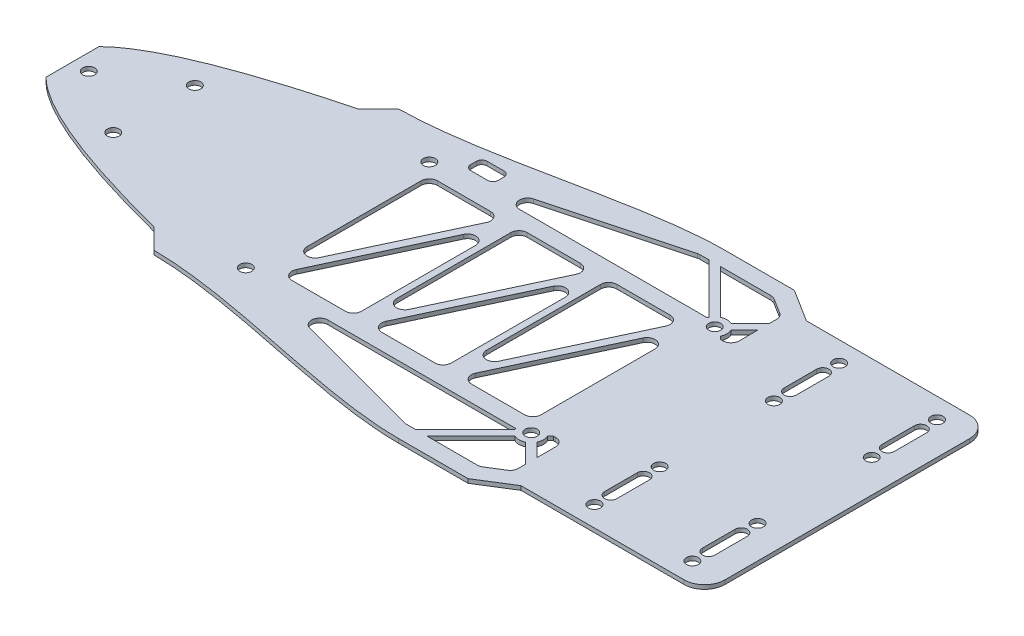
SolidWorks part; units mm, degrees
material "1060 Сплав"
ref_plane "Спереди" through (0, 0, 0) normal (0, 0, 1) x (1, 0, 0)
ref_plane "Сверху" through (0, 0, 0) normal (0, 1, 0) x (1, 0, 0)
ref_plane "Справа" through (0, 0, 0) normal (1, 0, 0) x (0, 0, -1)
sketch "Эскиз1" plane through (0, 0, 0) normal (0, 1, 0) x (1, 0, 0)
  line L0 (-109.2342, 0) -> (114.1892, 0) construction
  line L1 (95, -40) -> (-95, -40)
  line L2 (95, -40) -> (95, 40)
  line L3 (95, 40) -> (-95, 40)
  line L4 (-95, -40) -> (-95, 40)
  line L5 (95, -40) -> (-95, 40) construction
  line L6 (95, 40) -> (-95, -40) construction
  line L7 (50, 35) -> (42, 40)
  line L8 (95, 40) -> (50, 40)
  line L9 (95, 40) -> (95, 35)
  line L10 (95, 35) -> (50, 35)
  line L11 (50, 40) -> (50, 35)
  line L12 (95, -40) -> (50, -40)
  line L13 (95, -40) -> (95, -35)
  line L14 (95, -35) -> (50, -35)
  line L15 (50, -40) -> (50, -35)
  line L16 (50, -35) -> (42, -40)
  point P0 (0, 0)
  dimension "D1" = 190
  dimension "D2" = 80
  dimension "D3" = 45
  dimension "D4" = 70
  dimension "D5" = 8
extrude "Габариты" add sketch "Эскиз1" along normal blind 1 contours L16 L14 L2 L10 L7 L3 L4 L1 region at (-2.3466, 0, 0)
sketch "Эскиз2" plane through (0, 0, 0) normal (0, 1, 0) x (1, 0, 0)
  line L0 (-115.1505, 0) -> (106.9824, 0) construction
  line L1 (-95, -40) -> (-95, 40) construction
  line L2 (-95, 6.4911) -> (-95, -6.4911)
  line L3 (-95, 6.4911) -> (-95, -6.4911)
  line L5 (42, 40) -> (-95, 40) construction
  line L6 (42, -40) -> (-95, -40) construction
  line L7 (25, 40) -> (-95, 40)
  line L9 (-95, 40) -> (-95, 6.4911)
  line L10 (-95, -6.4911) -> (-95, -40)
  line L11 (-95, -40) -> (25, -40)
  line L12 (-50, 25.0267) -> (-45, 30)
  line L13 (-50, -25.0267) -> (-45, -30)
  parabola Q0 (25, -40) -> (25, 40) focus (-95, 0) apex (-98.2456, 0)
  spline S0 degree 3 poles (-45, 30) (-23.3831, 30.2616) (4.7804, 40) (25, 40) knots 0 0 0 0 1 1 1 1
  spline S1 degree 3 poles (-45, -30) (-23.3831, -30.2616) (4.7804, -40) (25, -40) knots 0 0 0 0 1 1 1 1
  point P15 (-95, 0)
  dimension "D1" = 120
  dimension "D2" = 45
  dimension "D3" = 50
  dimension "D4" = 60
extrude "Форма основы" cut sketch "Эскиз2" along normal through all contours L9 Q0 L7 | L11 Q0 L10 region at (-61.4598, 0, 30.4598) region at (-61.4598, 0, -30.4598)
sketch "Эскиз3" plane through (0, 0, 0) normal (0, 1, 0) x (1, 0, 0)
  line L0 (-107.3808, 0) -> (106.9824, 0) construction
  line L1 (75, 38.7487) -> (75, -39.5456) construction
  line L2 (95, 35) -> (50, 35) construction
  line L3 (63, 26) -> (63, 18) construction
  line L4 (95, -35) -> (95, 35) construction
  line L5 (64.5, 26) -> (64.5, 18)
  line L6 (61.5, 26) -> (61.5, 18)
  line L7 (87, 26) -> (87, 18) construction
  line L8 (85.5, 26) -> (85.5, 18)
  line L9 (88.5, 26) -> (88.5, 18)
  line L10 (63, -26) -> (63, -18) construction
  line L11 (64.5, -26) -> (64.5, -18)
  line L12 (61.5, -26) -> (61.5, -18)
  line L13 (87, -26) -> (87, -18) construction
  line L14 (85.5, -26) -> (85.5, -18)
  line L15 (88.5, -26) -> (88.5, -18)
  line L16 (95, -35) -> (50, -35) construction
  line L20 (95, -35) -> (95, -30)
  line L21 (95, 35) -> (90, 35)
  line L22 (95, -35) -> (90, -35)
  line L24 (95, 30) -> (95, 35)
  circle A0 centre (63, 30) radius 1.475
  circle A1 centre (63, 14) radius 1.475
  circle A2 centre (87, 14) radius 1.475
  circle A3 centre (87, 30) radius 1.475
  circle A4 centre (87, -14) radius 1.475
  circle A5 centre (87, -30) radius 1.475
  circle A6 centre (63, -14) radius 1.475
  circle A7 centre (63, -30) radius 1.475
  arc A8 (64.5, 26) -> (61.5, 26) centre (63, 26) ccw
  arc A9 (61.5, 18) -> (64.5, 18) centre (63, 18) ccw
  arc A10 (85.5, 26) -> (88.5, 26) centre (87, 26) cw
  arc A11 (88.5, 18) -> (85.5, 18) centre (87, 18) cw
  arc A12 (64.5, -26) -> (61.5, -26) centre (63, -26) cw
  arc A13 (61.5, -18) -> (64.5, -18) centre (63, -18) cw
  arc A14 (85.5, -26) -> (88.5, -26) centre (87, -26) ccw
  arc A15 (88.5, -18) -> (85.5, -18) centre (87, -18) ccw
  arc A16 (90, -35) -> (95, -30) centre (90, -30) ccw
  arc A17 (95, 30) -> (90, 35) centre (90, 30) ccw
  point P11 (63, 22)
  point P34 (87, 22)
  point P41 (63, -22)
  point P48 (87, -22)
  dimension "D2" = 2.95
  dimension "D9" = 5
  dimension "D4" = 16
  dimension "D5" = 5
  dimension "D3" = 24
  dimension "D1" = 20
  dimension "D6" = 4
  dimension "D7" = 4
  dimension "D8" = 3
extrude "Крепёж колёс" cut sketch "Эскиз3" along direction (0, 1, 0) on the side of the normal through all
sketch "Эскиз5" plane through (0, 0, 0) normal (0, 1, 0) x (1, 0, 0)
  line L0 (-94.6705, 0) -> (98.4358, 0) construction
  line L1 (-95, -6.4911) -> (-95, 6.4911) construction
  line L2 (-75, 10) -> (-75, -10) construction
  circle A0 centre (-75, 10) radius 1.475
  circle A1 centre (-75, -10) radius 1.475
  circle A2 centre (-91, 0) radius 1.475
  dimension "D1" = 2.95
  dimension "D4" = 16
  dimension "D2" = 20
  dimension "D3" = 20
extrude "Крепёж датчиков" cut sketch "Эскиз5" along normal blind 3
sketch "Эскиз6" plane through (0, 0, 0) normal (0, 1, 0) x (1, 0, 0)
  line L0 (-93.9533, 0) -> (93.2361, 0) construction
  circle A0 centre (-30, 22.5) radius 1.475
  circle A1 centre (40, 22.5) radius 1.475
  circle A2 centre (40, -22.5) radius 1.475
  circle A3 centre (-30, -22.5) radius 1.475
  dimension "D1" = 2.95
  dimension "D2" = 70
  dimension "D3" = 45
  dimension "D4" = 20
extrude "Крепёж платы" cut sketch "Эскиз6" along normal up to next
sketch "Эскиз7" plane through (0, 0, 0) normal (0, 1, 0) x (1, 0, 0)
  line L0 (-93.5382, 0) -> (96.5724, 0) construction
  line L6 (-30, -22.5) -> (40, 22.5) construction
  line L7 (-30, 22.5) -> (40, -22.5) construction
  line L10 (-8.6072, -19.5) -> (-21.6539, -19.5)
  line L12 (-11.9534, 19.5) -> (-25, 19.5)
  line L13 (-27, -10.4786) -> (-27, 17.5)
  line L14 (13.9587, -12.1877) -> (-30, 22.5) construction
  line L16 (-23.1874, -11.3238) -> (-10.1408, 16.6548)
  line L18 (-10.4199, 11.3238) -> (-23.4665, -16.6548)
  line L20 (-6.6072, -17.5) -> (-6.6072, 10.4786)
  line L33 (-5, -10.4786) -> (-5, 17.5)
  line L34 (-5, 23.9923) -> (-5, -26.1687) construction
  line L35 (-27, -10.4786) -> (-27, -19.5) construction
  line L36 (-6.6072, 10.4786) -> (-6.6072, 19.5) construction
  line L37 (-21.6539, -19.5) -> (-27, -19.5) construction
  line L38 (-11.9534, 19.5) -> (-6.6072, 19.5) construction
  line L39 (-25, -12.4786) -> (-19.3057, -12.4786)
  line L40 (-8.6072, 12.4786) -> (-10.7097, 12.4786)
  line L41 (10.0466, 19.5) -> (-3, 19.5)
  line L42 (-1.1874, -11.3238) -> (11.8592, 16.6548)
  line L43 (11.5801, 11.3238) -> (-1.4665, -16.6548)
  line L44 (15.3928, -17.5) -> (15.3928, 10.4786)
  line L45 (13.3928, -19.5) -> (0.3461, -19.5)
  line L46 (17, -10.4786) -> (17, 17.5)
  line L47 (32.0466, 19.5) -> (19, 19.5)
  line L48 (20.8126, -11.3238) -> (33.8592, 16.6548)
  line L49 (33.5801, 11.3238) -> (20.5335, -16.6548)
  line L50 (37.3928, -17.5) -> (37.3928, 10.4786)
  line L51 (35.3928, -19.5) -> (22.3461, -19.5)
  arc A0 (-11.9534, 19.5) -> (-10.1408, 16.6548) centre (-11.9534, 17.5) cw
  arc A1 (-25, 19.5) -> (-27, 17.5) centre (-25, 17.5) ccw
  arc A2 (-27, -10.4786) -> (-23.1874, -11.3238) centre (-25, -10.4786) ccw
  arc A3 (-23.4665, -16.6548) -> (-21.6539, -19.5) centre (-21.6539, -17.5) ccw
  arc A4 (-8.6072, -19.5) -> (-6.6072, -17.5) centre (-8.6072, -17.5) ccw
  arc A5 (-6.6072, 10.4786) -> (-10.4199, 11.3238) centre (-8.6072, 10.4786) ccw
  arc A6 (-3, 19.5) -> (-5, 17.5) centre (-3, 17.5) ccw
  arc A7 (10.0466, 19.5) -> (11.8592, 16.6548) centre (10.0466, 17.5) cw
  arc A8 (-5, -10.4786) -> (-1.1874, -11.3238) centre (-3, -10.4786) ccw
  arc A9 (15.3928, 10.4786) -> (11.5801, 11.3238) centre (13.3928, 10.4786) ccw
  arc A10 (13.3928, -19.5) -> (15.3928, -17.5) centre (13.3928, -17.5) ccw
  arc A11 (-1.4665, -16.6548) -> (0.3461, -19.5) centre (0.3461, -17.5) ccw
  arc A12 (19, 19.5) -> (17, 17.5) centre (19, 17.5) ccw
  arc A13 (32.0466, 19.5) -> (33.8592, 16.6548) centre (32.0466, 17.5) cw
  arc A14 (17, -10.4786) -> (20.8126, -11.3238) centre (19, -10.4786) ccw
  arc A15 (37.3928, 10.4786) -> (33.5801, 11.3238) centre (35.3928, 10.4786) ccw
  arc A16 (35.3928, -19.5) -> (37.3928, -17.5) centre (35.3928, -17.5) ccw
  arc A17 (20.5335, -16.6548) -> (22.3461, -19.5) centre (22.3461, -17.5) ccw
  point P32 (-6.6072, 19.5)
  dimension "D1" = 3
  dimension "D4" = 2
  dimension "D5" = 2
  dimension "D7" = 3
  dimension "D2" = 3
  dimension "D3" = 25
  dimension "D6" = 2
extrude "Облегчение 1" cut sketch "Эскиз7" along normal through all contours L16 A0 L12 A1 L13 A2 | L18 A3 L10 A4 L20 A5 | L33 A6 L41 A7 L42 A8 | L43 A11 L45 A10 L44 A9 | L46 A12 L47 A13 L48 A14 | L49 A17 L51 A16 L50 A15
sketch "Эскиз8" plane through (0, 0, 0) normal (0, 1, 0) x (1, 0, 0)
  line L0 (-98.4956, 0) -> (99.5433, 0) construction
  line L1 (37.1716, 23.5) -> (-8.8722, 23.5)
  line L2 (-9.3898, 27.4319) -> (24.5577, 36.5281)
  line L3 (22.8502, 36) -> (40.2792, 36)
  line L4 (46, 31.6745) -> (46, 25.5)
  line L6 (32.0466, 19.5) -> (19, 19.5) construction
  line L7 (42, 40) -> (25, 40) construction
  line L8 (41.3392, 35.696) -> (47.7654, 31.6796)
  line L9 (50, 35) -> (42, 40) construction
  line L10 (40, 22.5) -> (16.1502, 46.3498) construction
  line L11 (40, 22.5) -> (55.2262, 37.7262) construction
  line L16 (41.2929, 25.2071) -> (47.7654, 31.6796)
  line L17 (38.7071, 25.2071) -> (26.7884, 37.1258)
  line L18 (24.5577, 36.5281) -> (37.2929, 23.7929)
  line L19 (42.7071, 23.7929) -> (49.506, 30.5918)
  line L20 (26.7884, 37.1258) -> (22.3326, 35.9319)
  line L21 (49.506, 30.5918) -> (45.06, 33.3705)
  line L22 (46, -31.6745) -> (46, -25.5)
  line L23 (49.506, -30.5918) -> (45.06, -33.3705)
  line L25 (42.7071, -23.7929) -> (49.506, -30.5918)
  line L26 (41.2929, -25.2071) -> (47.7654, -31.6796)
  line L27 (22.8502, -36) -> (40.2792, -36)
  line L28 (26.7884, -37.1258) -> (22.3326, -35.9319)
  line L29 (38.7071, -25.2071) -> (26.7884, -37.1258)
  line L30 (24.5577, -36.5281) -> (37.2929, -23.7929)
  line L31 (37.1716, -23.5) -> (-8.8722, -23.5)
  line L32 (-9.3898, -27.4319) -> (24.5577, -36.5281)
  line L33 (41.3392, -35.696) -> (47.7654, -31.6796)
  line L34 (42.2361, 20.5) -> (44, 20.5)
  line L35 (46, 22.5) -> (46, 25.5)
  line L36 (46, -22.5) -> (46, -25.5)
  line L37 (43.4142, -20.5) -> (44, -20.5)
  line L38 (38.7071, 25.2071) -> (43.8114, 20.1028) construction
  line L39 (42.7071, 21.2071) -> (43.4142, 20.5)
  line L40 (42.7071, -21.2071) -> (43.4142, -20.5)
  arc A0 (37.1716, 23.5) -> (37.2929, 23.7929) centre (40, 22.5) cw
  arc A1 (45.06, 33.3705) -> (46, 31.6745) centre (44, 31.6745) cw
  arc A2 (41.3392, 35.696) -> (40.2792, 36) centre (40.2792, 34) ccw
  arc A3 (22.3326, 35.9319) -> (22.8502, 36) centre (22.8502, 34) cw
  arc A5 (-8.8722, 23.5) -> (-9.3898, 27.4319) centre (-8.8722, 25.5) cw
  arc A6 (38.7071, 25.2071) -> (41.2929, 25.2071) centre (40, 22.5) cw
  arc A7 (42.7071, 23.7929) -> (37.0287, 22.9143) centre (40, 22.5) cw
  arc A9 (45.06, -33.3705) -> (46, -31.6745) centre (44, -31.6745) ccw
  arc A10 (42.7071, -23.7929) -> (37.0287, -22.9143) centre (40, -22.5) ccw
  arc A11 (41.3392, -35.696) -> (40.2792, -36) centre (40.2792, -34) cw
  arc A12 (38.7071, -25.2071) -> (41.2929, -25.2071) centre (40, -22.5) ccw
  arc A13 (22.3326, -35.9319) -> (22.8502, -36) centre (22.8502, -34) ccw
  arc A14 (37.1716, -23.5) -> (37.2929, -23.7929) centre (40, -22.5) ccw
  arc A15 (-8.8722, -23.5) -> (-9.3898, -27.4319) centre (-8.8722, -25.5) ccw
  arc A16 (37.0287, 22.9143) -> (42.2361, 20.5) centre (40, 22.5) cw
  arc A17 (44, 20.5) -> (46, 22.5) centre (44, 22.5) ccw
  arc A18 (44, -20.5) -> (46, -22.5) centre (44, -22.5) cw
  arc A19 (37.0287, -22.9143) -> (42.7071, -21.2071) centre (40, -22.5) ccw
  dimension "D1" = 3
  dimension "D7" = 2
  dimension "D12" = 2
  dimension "D2" = 4
  dimension "D3" = 4
  dimension "D4" = 4
  dimension "D5" = 4
  dimension "D6" = 15
  dimension "D8" = 45
  dimension "D9" = 90
  dimension "D10" = 2
  dimension "D11" = 2
  dimension "D13" = 3
extrude "Облегчение 2" cut sketch "Эскиз8" along normal through all contours A5 L1 A0 L18 L2 | L17 A6 L16 L8 A2 L3 A3 L20 | L19 A7 L4 A1 L21 | A10 L25 L23 A9 L22 | L31 A15 L32 L30 A14 | L28 A13 L27 A11 L26 A10 L29 region at (14.4825, 0, -28.0349) region at (38.4145, 0, -31.5748) region at (44.5637, 0, -23.2443) region at (38.4145, 0, 31.5748) region at (44.5637, 0, 23.2443) region at (14.4825, 0, 28.0349)
sketch "Эскиз10" plane through (0, 1, 0) normal (0, 1, 0) x (1, 0, 0)
  line L0 (-30, 22.5) -> (-30, 28.9202)
  line L1 (-30, 28.9202) -> (-24.37, 28.9202)
  line L2 (-24.37, 28.9202) -> (-24.37, 27.0152)
  line L3 (-23.1, 25.7452) -> (-18.909, 25.7452)
  line L4 (-17.639, 27.0152) -> (-17.639, 28.9202)
  line L5 (-17.639, 28.9202) -> (-11.7335, 28.9202)
  line L7 (-24.37, 25.7452) -> (-17.639, 25.7452)
  line L8 (-24.37, 25.7452) -> (-24.37, 28.4752)
  line L9 (-23.1, 29.7452) -> (-18.909, 29.7452)
  line L10 (-17.639, 25.7452) -> (-17.639, 28.4752)
  arc A0 (-18.909, 29.7452) -> (-17.639, 28.4752) centre (-18.909, 28.4752) cw
  arc A1 (-18.909, 25.7452) -> (-17.639, 27.0152) centre (-18.909, 27.0152) ccw
  arc A2 (-24.37, 27.0152) -> (-23.1, 25.7452) centre (-23.1, 27.0152) ccw
  arc A3 (-24.37, 28.4752) -> (-23.1, 29.7452) centre (-23.1, 28.4752) cw
  dimension "D2" = 1.27
  dimension "D1" = 6.4202
  dimension "D3" = 4
  dimension "D4" = 6.731
extrude "Провода питания" cut sketch "Эскиз10" against normal through all contours A3 L2 A2 L3 A1 L4 A0 L9 region at (-21.0045, 1, -27.7452)
equation "\"D7@Эскиз3\"=\"D6@Эскиз3\""
equation "\"D4@Эскиз8\"=\"D3@Эскиз8\""
equation "\"D5@Эскиз8\"=\"D3@Эскиз8\""
equation "\"D11@Эскиз8\"=\"D10@Эскиз8\""
